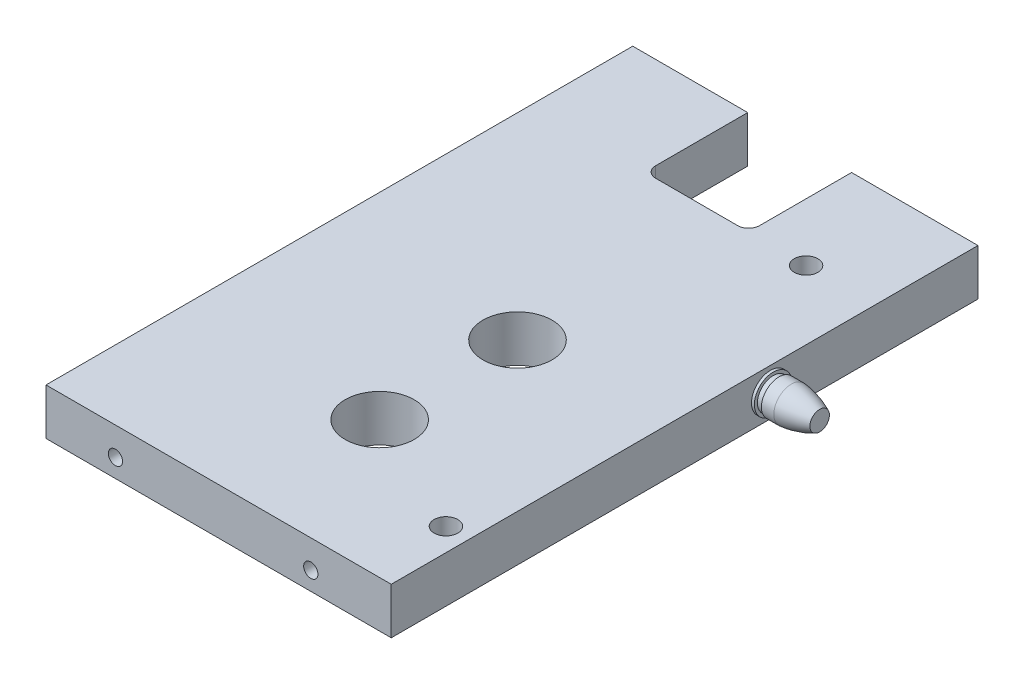
SolidWorks part; units mm, degrees
material "1060 Alloy"
ref_plane "Front Plane" through (0, 0, 0) normal (0, 0, 1) x (1, 0, 0)
ref_plane "Top Plane" through (0, 0, 0) normal (0, 1, 0) x (1, 0, 0)
ref_plane "Right Plane" through (0, 0, 0) normal (1, 0, 0) x (0, 0, -1)
sketch "Sketch1" plane through (0, 0, 0) normal (0, 0, 1) x (1, 0, 0)
  line L0 (-234.625, -82.5) -> (-329.875, -82.5) construction
  line L1 (-234.625, -88.9) -> (-329.875, -88.9)
  line L2 (-234.625, -88.9) -> (-234.625, -76.1)
  line L3 (-234.625, -76.1) -> (-329.875, -76.1)
  line L4 (-329.875, -88.9) -> (-329.875, -76.1)
  line L7 (-329.875, -610.1) -> (-329.875, -622.9) construction
  line L8 (-234.625, -610.1) -> (-234.625, -622.9) construction
  circle A0 centre (-308, -82.5) radius 3.1
  circle A1 centre (-320.5, -82.5) radius 2.395
  circle A2 centre (-244.2, -82.5) radius 2.395
  circle A3 centre (-257.2, -82.5) radius 3.1
  circle A9 centre (-308, -82.5) radius 3.1 construction
  circle A10 centre (-257.2, -82.5) radius 3.1 construction
  circle A11 centre (-244.2, -82.5) radius 3.425 construction
  circle A12 centre (-320.5, -82.5) radius 3.425 construction
  circle A13 centre (-320.5, -616.5) radius 2.395 construction
extrude "Boss-Extrude1" add sketch "Sketch1" along normal up to surface (161.88 mm away) contours L3 L4 L1 L2
extrude "Cut-Extrude1" cut sketch "Sketch1<3>" along normal up to surface (20.2 mm away) contours A0 L0 | A3 L0 | L0 A0 | L0 A3 region at (-257.2, -83.8157, 0) region at (-257.2, -81.1843, 0) region at (-308, -83.8157, 0) region at (-308, -81.1843, 0)
sketch "Sketch1<3>" plane through (0, 0, 0) normal (0, 0, 1) x (1, 0, 0) same geometry as "Sketch1"
extrude "Cut-Extrude2" cut sketch "Sketch1<4>" along normal up to surface (21.5 mm away) contours L0 A2 | A2 L0 | L0 A1 | A1 L0 region at (-244.2, -83.5165, 0) region at (-244.2, -81.4835, 0) region at (-320.5, -81.4835, 0) region at (-320.5, -83.5165, 0)
sketch "Sketch1<4>" plane through (0, 0, 0) normal (0, 0, 1) x (1, 0, 0) same geometry as "Sketch1"
sketch "Sketch2" plane through (0, -76.1, 0) normal (0, 1, 0) x (-1, 0, 0)
  line L3 (269.505, 25.4) -> (269.505, 0)
  line L4 (295.155, 28.4) -> (272.505, 28.4)
  line L5 (298.155, 0) -> (298.155, 25.4)
  line L6 (269.505, 0) -> (298.155, 0)
  line L7 (295.155, 28.4) -> (272.505, 28.4) construction
  line L8 (269.505, 25.4) -> (269.505, 0) construction
  line L9 (298.155, 0) -> (298.155, 25.4) construction
  line L10 (234.625, 0) -> (329.875, 0) construction
  arc A6 (272.505, 28.4) -> (269.505, 25.4) centre (272.505, 25.4) ccw
  arc A7 (298.155, 25.4) -> (295.155, 28.4) centre (295.155, 25.4) ccw
  circle A8 centre (275.57, 86.105) radius 9.525
  circle A9 centre (275.57, 124.135) radius 9.525
  circle A10 centre (253.55, 28.505) radius 3.265
  circle A11 centre (240.925, 140.49) radius 3.265
  arc A12 (272.505, 28.4) -> (269.505, 25.4) centre (272.505, 25.4) ccw construction
  arc A13 (298.155, 25.4) -> (295.155, 28.4) centre (295.155, 25.4) ccw construction
  circle A14 centre (275.57, 86.105) radius 9.525 construction
  circle A15 centre (275.57, 124.135) radius 9.525 construction
  circle A16 centre (240.925, 140.49) radius 3.265 construction
  circle A17 centre (253.55, 28.505) radius 3.265 construction
extrude "Cut-Extrude3" cut sketch "Sketch2" against normal up to next
sketch "Sketch3" plane through (0, -88.9, 0) normal (0, -1, 0) x (1, 0, 0)
  circle A2 centre (-240.925, 140.49) radius 3.265
  circle A3 centre (-253.55, 28.505) radius 9.525
  circle A4 centre (-253.55, 28.505) radius 9.525 construction
  circle A6 centre (-240.925, 140.49) radius 3.265 construction
extrude "Cut-Extrude4" cut sketch "Sketch3" against normal blind 3.32
sketch "Sketch4" plane through (0, 0, 161.88) normal (0, 0, 1) x (1, 0, 0)
  circle A0 centre (-256.825, -83.83) radius 1.965
  circle A1 centre (-310.715, -83.83) radius 1.965
  circle A5 centre (-256.825, -83.83) radius 2.795 construction
  circle A6 centre (-310.715, -83.83) radius 2.795 construction
  dimension "D1" = 3.93
extrude "Cut-Extrude5" cut sketch "Sketch4" against normal up to surface (17.25 mm away)
ref_plane "Plane1" through (0, -82.5, 0) normal (0, 1, 0) x (-1, 0, 0)
sketch "Sketch5" plane through (0, -82.5, 0) normal (0, 1, 0) x (-1, 0, 0)
  line L9 (234.625, 57.29) -> (259.3185, 57.29) construction
  line L10 (234.625, 57.29) -> (221.025, 57.29) construction
  line L11 (221.025, 57.29) -> (221.025, 54.59) construction
  line L12 (232.2758, 52.475) -> (228.8458, 52.475) construction
  line L13 (232.295, 52.925) -> (232.2758, 52.475) construction
  line L14 (233.835, 52.925) -> (232.295, 52.925) construction
  line L15 (233.835, 52.09) -> (233.835, 52.925) construction
  line L16 (234.625, 52.09) -> (233.835, 52.09) construction
  line L17 (234.625, 57.29) -> (234.625, 52.09) construction
  line L18 (234.625, 57.29) -> (259.3185, 57.29) construction
  line L19 (234.625, 57.29) -> (221.025, 57.29)
  line L20 (221.025, 57.29) -> (221.025, 54.59)
  line L21 (232.2758, 52.475) -> (228.8458, 52.475)
  line L22 (232.295, 52.925) -> (232.2758, 52.475)
  line L23 (233.835, 52.925) -> (232.295, 52.925)
  line L24 (233.835, 52.09) -> (233.835, 52.925)
  line L25 (234.625, 52.09) -> (233.835, 52.09)
  line L26 (234.625, 57.29) -> (234.625, 52.09)
  arc A1 (221.025, 54.59) -> (228.8458, 52.475) centre (230.8458, 75.3879) ccw construction
  arc A2 (221.025, 54.59) -> (228.8458, 52.475) centre (230.8458, 75.3879) ccw
revolve "Revolve1" add sketch "Sketch5" angle 360 about L18
